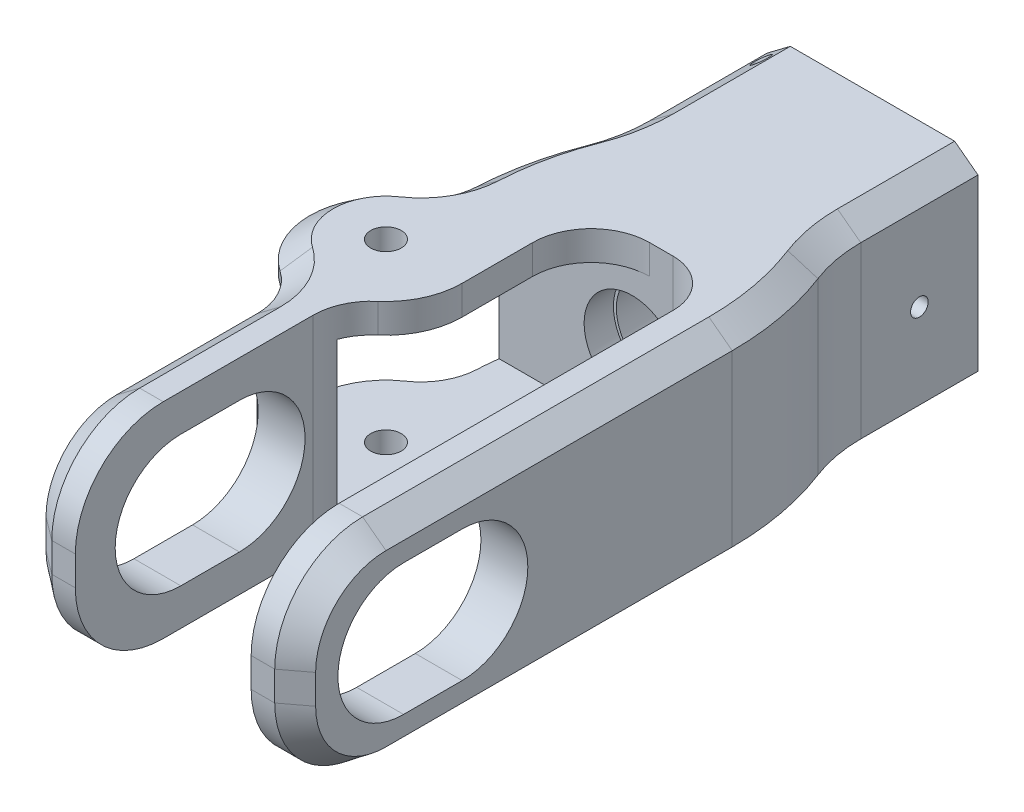
SolidWorks part; units mm, degrees
ref_plane "Front Plane" through (0, 0, 0) normal (0, 0, 1) x (1, 0, 0)
ref_plane "Top Plane" through (0, 0, 0) normal (0, 1, 0) x (1, 0, 0)
ref_plane "Right Plane" through (0, 0, 0) normal (1, 0, 0) x (0, 0, -1)
sketch "Sketch1" plane through (0, 0, 0) normal (0, 0, 1) x (1, 0, 0)
  line L1 (23, 17.5) -> (-23, 17.5)
  line L2 (23, 17.5) -> (23, -17.5)
  line L3 (23, -17.5) -> (-23, -17.5)
  line L4 (-23, 17.5) -> (-23, -17.5)
  line L5 (23, 17.5) -> (-23, -17.5) construction
  line L6 (23, -17.5) -> (-23, 17.5) construction
  circle A0 centre (0, 0) radius 7.7
  dimension "D1" = 15.4
  dimension "D2" = 46
  dimension "D3" = 35
extrude "Boss-Extrude1" add sketch "Sketch1" along normal blind 36
sketch "Sketch2" plane through (0, 0, 0) normal (0, 0, -1) x (-1, 0, 0)
  circle A0 centre (0, 0) radius 7.7
  circle A1 centre (0, 0) radius 11
  circle A2 centre (0, 0) radius 7.7 construction
  dimension "D1" = 22
extrude "Boss-Extrude2" add sketch "Sketch2" along normal blind 1
sketch "Sketch5" plane through (0, 0, 36) normal (0, 0, 1) x (1, 0, 0)
  line L0 (-23, -17.5) -> (23, -17.5) construction
  line L1 (-23, 17.5) -> (-15, 17.5)
  line L2 (-23, 17.5) -> (-23, -17.5)
  line L3 (-23, -17.5) -> (-15, -17.5)
  line L4 (-15, 17.5) -> (-15, -17.5)
  dimension "D1" = 8
extrude "Boss-Extrude4" add sketch "Sketch5" along normal blind 85
sketch "Sketch3" plane through (0, 0, 36) normal (0, 0, 1) x (1, 0, 0)
  line L1 (-15, 17.5) -> (23, 17.5)
  line L2 (-15, 17.5) -> (-15, -17.5)
  line L3 (-15, -17.5) -> (23, -17.5)
  line L4 (23, 17.5) -> (23, -17.5)
  circle A0 centre (0, 0) radius 8.2
  dimension "D1" = 16.4
extrude "Boss-Extrude3" add sketch "Sketch3" along normal blind 5
sketch "Sketch4" plane through (0, 0, 0) normal (0, 1, 0) x (1, 0, 0)
  line L0 (23, -41) -> (-15, -41) construction
  circle A0 centre (-20, -63) radius 2.6
  dimension "D2" = 5.2
  dimension "D1" = 22
  dimension "D3" = 20
extrude "Cut-Extrude1" cut sketch "Sketch4" against normal through all both and the other way through all
sketch "Sketch10" plane through (0, 17.5, 0) normal (0, 1, 0) x (1, 0, 0)
  line L0 (-23, -121) -> (-23, 0) construction
  line L1 (-23, -50.3509) -> (-23, -75.6491)
  line L2 (-15, -121) -> (-15, -41) construction
  line L3 (-15, -41) -> (-15, -75)
  line L4 (-7, -63) -> (-7, -41)
  line L5 (23, -41) -> (-15, -41) construction
  line L6 (-7, -41) -> (-15, -41)
  arc A0 (-23, -50.3509) -> (-23, -75.6491) centre (-20, -63) ccw
  arc A2 (-15, -75) -> (-7, -63) centre (-20, -63) ccw
  dimension "D1" = 13
  dimension "D2" = 13
extrude "Boss-Extrude6" add sketch "Sketch10" against normal up to surface (35 mm away) up to face at (-20, -17.5, 65.6)
sketch "Sketch6" plane through (0, 0, 0) normal (0, 1, 0) x (1, 0, 0)
  line L5 (-33, -41) -> (-33, -77)
  line L6 (-33, -77) -> (-7, -77)
  line L7 (-7, -77) -> (-7, -41)
  line L8 (-7, -41) -> (-33, -41)
  circle A0 centre (-20, -63) radius 2.6 construction
  point P0 (-20, -59)
  point P3 (-33, -59)
  point P5 (-9, -41)
  point P7 (-8.5054, -41.0554)
  point P8 (-20, -41)
  point P12 (-20, -77)
  dimension "D1" = 14
  dimension "D2" = 26
sketch "Sketch9" plane through (0, 0, 41) normal (0, 0, 1) x (1, 0, 0)
  line L0 (-7, -17.5) -> (23, -17.5) construction
  line L1 (23, 17.5) -> (15, 17.5)
  line L2 (23, 17.5) -> (23, -17.5)
  line L3 (23, -17.5) -> (15, -17.5)
  line L4 (15, 17.5) -> (15, -17.5)
  line L5 (23, 17.5) -> (-7, 17.5) construction
  point P4 (25, -17.5)
  dimension "D1" = 8
extrude "Boss-Extrude5" add sketch "Sketch9" along normal blind 80
fillet "Fillet1" radius 15 4 edges at (-19, -17.5, 121) (-19, 17.5, 121) (19, -17.5, 121) (19, 17.5, 121)
fillet "Fillet9" radius 10 3 edges at (-23, 0, 50.3509) (-23, 0, 75.6491) (-15, 0, 75)
fillet "Fillet11" radius 8 1 edges at (15, 0, 41)
sketch "Sketch20" plane through (0, 17.5, 0) normal (0, 1, 0) x (1, 0, 0)
  line L0 (-18, 0) -> (-18, -20)
  line L1 (-23, -44.0263) -> (-23, 0) construction
  line L2 (23, 0) -> (-23, 0) construction
  line L3 (-18, 0) -> (-23, 0)
  line L4 (-23, 0) -> (-23, -35)
  line L5 (18, -20) -> (18, 0)
  line L6 (18, 0) -> (23, 0)
  line L7 (23, 0) -> (23, -35)
  line L8 (23, -106) -> (23, 0) construction
  arc A0 (-18, -20) -> (-23, -35) centre (-43, -20) cw
  arc A1 (23, -35) -> (18, -20) centre (43, -20) cw
  dimension "D2" = 25
  dimension "D1" = 5
  dimension "D3" = 35
  dimension "D4" = 5
extrude "Cut-Extrude2" cut sketch "Sketch20" against normal up to surface (35 mm away) up to face at (-20, -17.5, 65.6)
fillet "Fillet12" radius 50 2 edges at (23, 0, 35) (-23, 0, 35)
extrude "Cut-Extrude3" cut sketch "Sketch6" against normal mid plane 25
fillet "Fillet13" radius 10 2 edges at (-7, -15, 41) (-7, 15, 41)
ref_axis "Axis1" through (-20, 12.5, 63) along (0, 1, 0)
sketch "Sketch21" plane through (-23, 0, 0) normal (-1, 0, 0) x (0, 0, 1)
  line L1 (63, 12.5) -> (63, 17.5) construction
  line L2 (55, 0) -> (-55, 0) construction
  circle A0 centre (98, 0) radius 2.5 construction
  dimension "D2" = 5
  dimension "D1" = 35
sketch "Sketch22" plane through (-23, 0, 0) normal (-1, 0, 0) x (0, 0, 1)
  line L0 (93, 0) -> (103, 0) construction
  line L1 (93, 11.2) -> (103, 11.2)
  line L2 (93, -11.2) -> (103, -11.2)
  arc A0 (93, 11.2) -> (93, -11.2) centre (93, 0) ccw
  arc A1 (103, -11.2) -> (103, 11.2) centre (103, 0) ccw
  point P2 (98, 0)
  dimension "D1" = 22.4
  dimension "D2" = 10
extrude "Cut-Extrude4" cut sketch "Sketch22" against normal up to surface (46 mm away) up to face at (23, 0, 92.3441)
chamfer "Chamfer1" distance 3 angle 53 28 edges at (18, -17.5, 10) (18.4202, -17.5, 24.5644) (22.1596, -17.5, 37.7971) (23, -17.5, 76.4629) (23, -13.1066, 116.6066) (18, 17.5, 10) (23, 0, 121) (18.4202, 17.5, 24.5644) (23, 13.1066, 116.6066) (22.1596, 17.5, 37.7971) (23, 17.5, 76.4629) (-18, -17.5, 10) (-18.427, -17.5, 24.601) (-21.9716, -17.5, 36.6622) (-24.2773, -17.5, 48.9165) (-33, -17.5, 63) (-24.1535, -17.5, 77.3111) (-23, -17.5, 93.9868) (-23, -13.1066, 116.6066) (-23, 0, 121) (-23, 13.1066, 116.6066) (-24.1535, 17.5, 77.3111) (-33, 17.5, 63) (-18, 17.5, 10) (-24.2773, 17.5, 48.9165) (-18.427, 17.5, 24.601) (-23, 17.5, 93.9868) (-21.9716, 17.5, 36.6622) first distance on face at (18, 0, 10) first distance on face at (18.6268, 0, 24.526) first distance on face at (21.7465, 0, 37.8738) first distance on face at (23, 0, 98) first distance on face at (-18, 0, 10) first distance on face at (-18.6369, 0, 24.5617) first distance on face at (-22.2682, 0, 39.7496) first distance on face at (-24.7289, -15, 48.6633) first distance on face at (-30.1739, -15, 63) first distance on face at (-24.763, 0, 77.5375) first distance on face at (-23, 0, 98.9959) first distance on face at (-30.1739, 15, 63) first distance on face at (-24.7289, 15, 48.6633)
sketch "Sketch23" plane through (18, 0, 0) normal (1, 0, 0) x (0, 0, -1)
  line L0 (0, -14.5) -> (0, 14.5) construction
  line L1 (55, 0) -> (-55, 0) construction
  circle A0 centre (-10, 0) radius 1.5
  dimension "D1" = 3
  dimension "D2" = 10
extrude "Cut-Extrude5" cut sketch "Sketch23" against normal up to surface (10.3 mm away) up to face at (7.7, 0, 36)
sketch "Sketch25" plane through (-13.4884, 17.8997, 0) normal (-0.6018, 0.7986, 0) x (0.7986, 0.6018, 0)
  line L0 (-5.6491, 0) -> (-0.6642, 0) construction
  circle A0 centre (-3.1567, -3) radius 1.5
  point P5 (-3.1567, 0)
  dimension "D1" = 3
  dimension "D2" = 3
extrude "Cut-Extrude6" cut sketch "Sketch25" against normal blind 10
